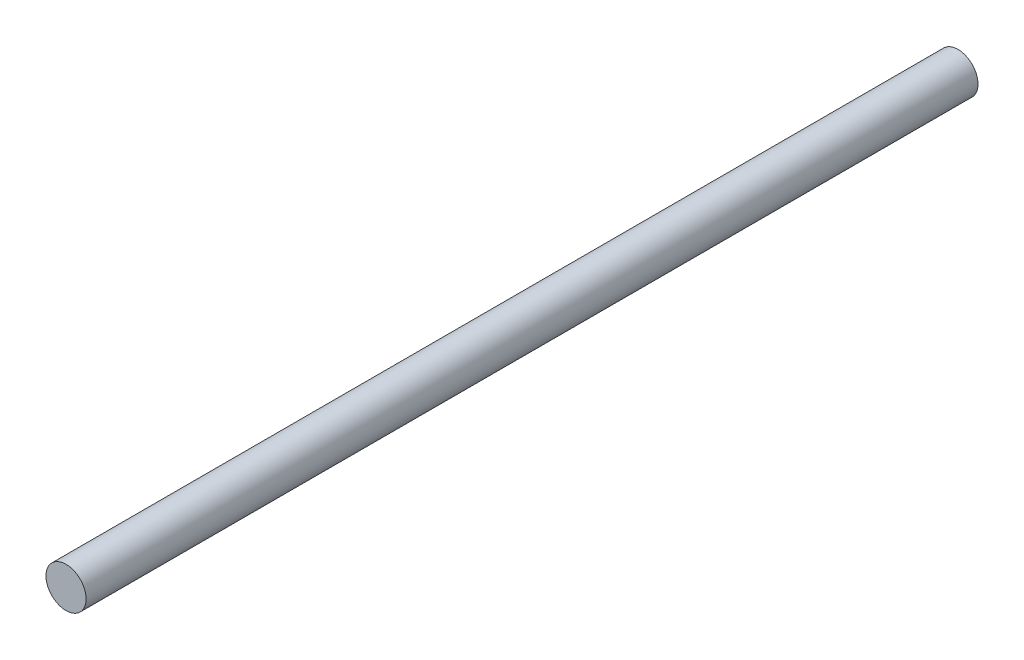
SolidWorks part; units mm, degrees
ref_plane "Front Plane" through (0, 0, 0) normal (0, 0, 1) x (1, 0, 0)
ref_plane "Top Plane" through (0, 0, 0) normal (0, 1, 0) x (1, 0, 0)
ref_plane "Right Plane" through (0, 0, 0) normal (1, 0, 0) x (0, 0, -1)
sketch "Sketch3" plane through (0, 0, 0) normal (0, 0, 1) x (1, 0, 0)
  circle A0 centre (0, 0) radius 4
  dimension "D1" = 8
extrude "Boss-Extrude1" add sketch "Sketch3" along normal blind 177.8
equation "\"l\"= 6"
